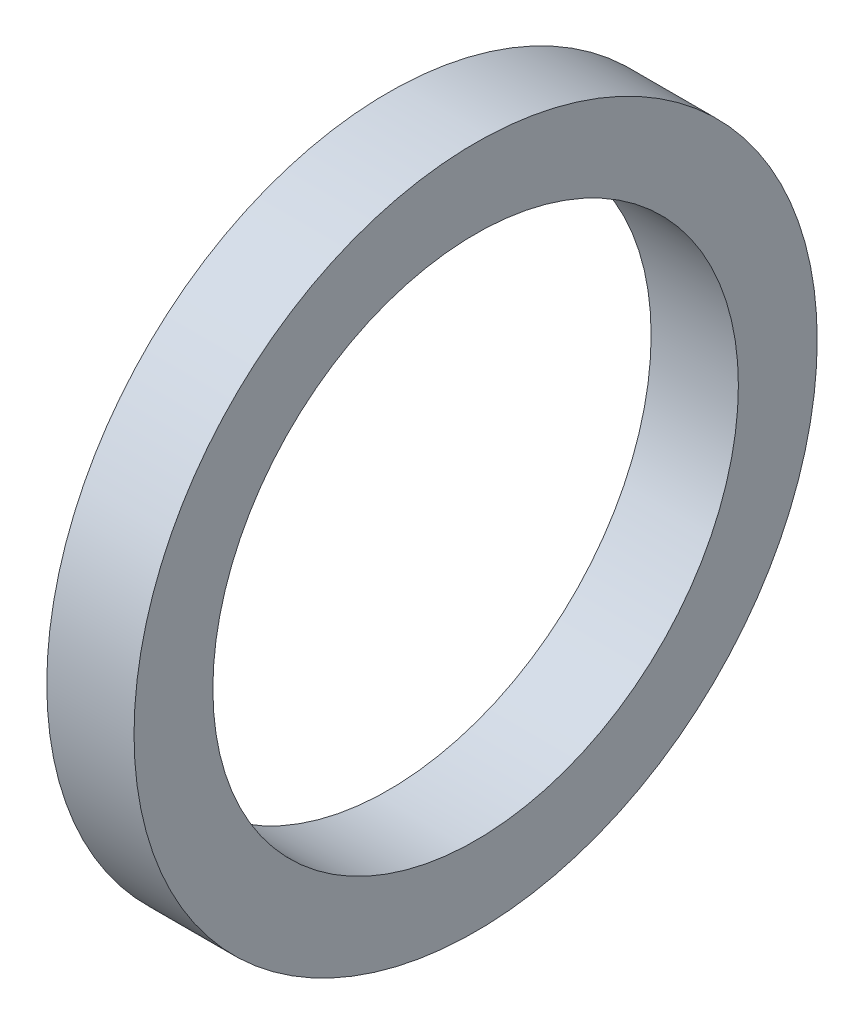
SolidWorks part; units mm, degrees
ref_plane "Front Plane" through (0, 0, 0) normal (0, 0, 1) x (1, 0, 0)
ref_plane "Top Plane" through (0, 0, 0) normal (0, 1, 0) x (1, 0, 0)
ref_plane "Right Plane" through (0, 0, 0) normal (1, 0, 0) x (0, 0, -1)
sketch "Sketch2" plane through (0, 0, 0) normal (0, 0, 1) x (1, 0, 0)
  line L0 (0, 0) -> (58.591, 0) construction
  line L2 (0, 0) -> (18.4, 0)
  line L3 (0, 0) -> (0, 2.5)
  line L4 (0, 2.5) -> (18.4, 2.5)
  line L5 (18.4, 0) -> (18.4, 2.5)
  line L6 (6, 2.5) -> (6, 6)
  line L11 (6, 6) -> (9.97, 6)
  line L16 (12.97, 6) -> (12.97, 3)
  line L17 (12.97, 3) -> (13.6304, 3)
  line L18 (13.6304, 3) -> (13.6304, 2.5)
  line L19 (13.6304, 2.5) -> (6, 2.5)
  line L22 (13.6304, 2.5) -> (16.1104, 2.5)
  line L23 (13.6304, 2.5) -> (13.6304, 4)
  line L24 (13.6304, 4) -> (16.1104, 4)
  line L25 (16.1104, 2.5) -> (16.1104, 4)
  line L27 (6, 6) -> (9.97, 6)
  line L28 (6, 6) -> (6, 9)
  line L29 (6, 9) -> (9.97, 9)
  line L30 (9.97, 6) -> (9.97, 9)
  line L31 (6, 9) -> (6, 8.25)
  line L32 (6, 8.25) -> (5, 8.25)
  line L33 (8.58, 22.001) -> (8.58, 12.476) construction
  line L34 (5, 12.476) -> (12.16, 12.476)
  line L35 (9.97, 9) -> (12.16, 9)
  line L36 (5, 7.5) -> (3, 7.5)
  line L37 (5, 8.25) -> (5, 12.476)
  line L38 (5, 7.5) -> (5, 14)
  line L39 (5, 14) -> (3, 14)
  line L40 (3, 7.5) -> (3, 14)
  line L41 (5, 22.001) -> (12.16, 22.001)
  line L42 (5, 22.001) -> (5, 30.1625)
  line L43 (5, 30.1625) -> (12.16, 30.1625)
  line L44 (12.16, 22.001) -> (12.16, 30.1625)
  line L49 (16.6304, 22.001) -> (16.6304, 7.5)
  line L51 (23.0104, 7.5) -> (23.0104, 6.5)
  line L54 (16.1104, 4) -> (13.6304, 4)
  line L56 (18.0304, 7.5) -> (23.0104, 7.5)
  line L57 (13.16, 22.001) -> (16.6304, 22.001)
  line L58 (16.1104, 3.5) -> (20.0104, 3.5)
  line L59 (29.9004, 14) -> (26.9004, 11)
  line L60 (4, 31.75) -> (18.0304, 31.75)
  line L61 (18.0304, 7.5) -> (23.0104, 7.5)
  line L62 (18.0304, 7.5) -> (18.0304, 12)
  line L63 (18.0304, 12) -> (23.0104, 12)
  line L64 (23.0104, 7.5) -> (23.0104, 12)
  line L65 (18.0304, 31.75) -> (18.0304, 12)
  line L66 (23.0104, 11) -> (26.9004, 11)
  line L67 (34.8004, 23) -> (31.3004, 19.5)
  line L68 (35.8004, 31) -> (38.7904, 33.99)
  line L69 (29.9004, 14) -> (29.9004, 15)
  line L70 (29.9004, 15) -> (22.9304, 15)
  line L71 (22.9304, 15) -> (21.0304, 15)
  line L72 (18.0304, 7.5) -> (16.6304, 7.5)
  line L73 (21.0304, 15) -> (21.0304, 43)
  line L74 (20.0304, 40) -> (10.0704, 40)
  line L75 (10.0704, 40) -> (4, 40)
  line L76 (21.0304, 43) -> (20.0304, 43)
  line L77 (22.9304, 15) -> (29.9004, 15)
  line L78 (22.9304, 15) -> (22.9304, 21)
  line L79 (22.9304, 21) -> (29.9004, 21)
  line L80 (29.9004, 15) -> (29.9004, 21)
  line L81 (10.0704, 40) -> (20.0304, 40)
  line L82 (10.0704, 40) -> (10.0704, 50)
  line L83 (10.0704, 50) -> (20.0304, 50)
  line L84 (20.0304, 40) -> (20.0304, 50)
  line L85 (4, 40) -> (4, 31.75)
  line L86 (12.97, 3) -> (12.97, 2.5)
  line L87 (31.3004, 19.5) -> (29.9004, 19.5)
  line L88 (21.51, 63.5) -> (21.51, 44)
  line L89 (21.51, 63.5) -> (25.9304, 63.5)
  line L90 (25.9304, 63.5) -> (25.9304, 25)
  line L91 (27.8304, 25) -> (25.9304, 25)
  line L92 (10.0704, 48) -> (9, 48)
  line L93 (9, 48) -> (9, 53.476)
  line L94 (9, 53.476) -> (20.0304, 53.476)
  line L95 (20.0304, 53.476) -> (20.0304, 50)
  line L96 (14.5152, 63.001) -> (14.5152, 53.476) construction
  line L97 (9, 63.001) -> (20.0304, 63.001)
  line L98 (9, 63.001) -> (9, 68.2625)
  line L99 (9, 68.2625) -> (20.0304, 68.2625)
  line L100 (20.0304, 63.001) -> (20.0304, 68.2625)
  line L101 (12.97, 6) -> (11.97, 6)
  line L102 (9, 42.5) -> (5, 42.5)
  line L103 (9, 42.5) -> (9, 55)
  line L104 (9, 55) -> (5, 55)
  line L105 (5, 42.5) -> (5, 55)
  line L106 (9.97, 6) -> (10.87, 6)
  line L107 (27.8304, 25) -> (34.8004, 25)
  line L108 (34.8004, 25) -> (34.8004, 23)
  line L109 (0, 0) -> (-2, 0)
  line L110 (0, 0) -> (0, 11)
  line L111 (27.8304, 25) -> (34.8004, 25)
  line L112 (27.8304, 25) -> (27.8304, 32.5)
  line L113 (27.8304, 32.5) -> (34.8004, 32.5)
  line L114 (34.8004, 25) -> (34.8004, 32.5)
  line L115 (35.8004, 31) -> (34.8004, 31)
  line L116 (27.8304, 32.5) -> (27.8304, 64.5)
  line L117 (21.1827, 74.025) -> (6.8477, 74.025)
  line L118 (6.8477, 74.025) -> (6.8477, 76.2)
  line L119 (38.7904, 47.29) -> (30.8304, 55.25)
  line L120 (0, 11) -> (-2, 11)
  line L121 (38.7904, 43.815) -> (30.8529, 43.815)
  line L123 (-4.8, 69.85) -> (1.55, 76.2)
  line L124 (38.7904, 47.29) -> (38.7904, 33.99)
  line L125 (-2, 0) -> (-2, 11)
  line L126 (38.7904, 37.465) -> (30.8529, 37.465)
  line L127 (30.8529, 43.815) -> (30.8529, 37.465)
  line L128 (6, 2.5) -> (6, 0)
  line L129 (0, 63.5) -> (0, 30)
  line L132 (5, 63.5) -> (0, 63.5)
  line L136 (-1.8, 30) -> (-11.76, 30)
  line L138 (-13.76, 25.4) -> (-2, 25.4)
  line L139 (-2, 25.4) -> (-2, 11.5)
  line L140 (27.8304, 64.5) -> (21.1827, 64.5)
  line L141 (-1.8, 30) -> (-11.76, 30)
  line L142 (-1.8, 30) -> (-1.8, 39)
  line L143 (-1.8, 39) -> (-11.76, 39)
  line L144 (-11.76, 30) -> (-11.76, 39)
  line L145 (21.1827, 64.5) -> (21.1827, 74.025)
  line L146 (-12.76, 37) -> (-12.76, 47.29)
  line L147 (-12.76, 37) -> (-11.76, 37)
  line L148 (30.8304, 55.25) -> (30.8304, 76.2)
  line L149 (11.97, 6) -> (11.97, 5.45)
  line L154 (-2, 11.5) -> (1, 11.5)
  line L155 (5, 60.6197) -> (24.05, 60.6197)
  line L160 (5, 60.6197) -> (5, 55.8572)
  line L161 (5, 55.8572) -> (24.05, 55.8572)
  line L166 (24.05, 60.6197) -> (24.05, 55.8572)
  line L167 (5, 60.6197) -> (24.05, 55.8572) construction
  line L172 (5, 55.8572) -> (24.05, 60.6197) construction
  line L173 (24.05, 62.2072) -> (25.9304, 62.2072)
  line L174 (11.97, 5.45) -> (10.87, 5.45)
  line L175 (10.87, 6) -> (10.87, 5.45)
  line L176 (24.05, 62.2072) -> (24.05, 54.2697)
  line L177 (24.05, 54.2697) -> (25.9304, 54.2697)
  line L178 (25.9304, 62.2072) -> (25.9304, 54.2697)
  line L179 (24.05, 62.2072) -> (25.9304, 54.2697) construction
  line L180 (24.05, 54.2697) -> (25.9304, 62.2072) construction
  line L181 (3, 19.6197) -> (15.7, 19.6197)
  line L182 (3, 19.6197) -> (3, 14.8572)
  line L183 (3, 14.8572) -> (15.7, 14.8572)
  line L184 (15.7, 19.6197) -> (15.7, 14.8572)
  line L185 (3, 19.6197) -> (15.7, 14.8572) construction
  line L186 (3, 14.8572) -> (15.7, 19.6197) construction
  line L187 (15.7, 21.2072) -> (16.6304, 21.2072)
  line L188 (15.7, 21.2072) -> (15.7, 13.2697)
  line L189 (15.7, 13.2697) -> (16.6304, 13.2697)
  line L190 (16.6304, 21.2072) -> (16.6304, 13.2697)
  line L191 (15.7, 21.2072) -> (16.6304, 13.2697) construction
  line L192 (15.7, 13.2697) -> (16.6304, 21.2072) construction
  line L193 (1, 11.5) -> (1, 6.5)
  line L194 (1, 6.5) -> (3, 6.5)
  line L195 (23.0104, 6.5) -> (20.0104, 3.5)
  line L196 (5, 63.5) -> (5, 42.5)
  line L197 (5, 42.5) -> (3, 42.5)
  line L198 (3, 42.5) -> (3, 6.5)
  line L199 (6, 0) -> (12.97, 0)
  line L200 (12.97, 0) -> (12.97, 2.5)
  line L201 (18.0304, 31.75) -> (18.0304, 35.875)
  line L202 (18.0304, 35.875) -> (21.0304, 35.875)
  line L203 (30.8304, 76.2) -> (6.8477, 76.2)
  line L204 (3.4027, 69.85) -> (7.8477, 69.85) construction
  line L205 (7.8477, 67.4687) -> (26.8977, 67.4688)
  line L206 (7.8477, 74.025) -> (7.8477, 64.5)
  line L207 (7.8477, 64.5) -> (-1.8, 64.5)
  line L208 (-1.8, 64.5) -> (-1.8, 39)
  line L209 (-12.76, 47.29) -> (-4.8, 55.25)
  line L210 (-4.8, 55.25) -> (-4.8, 69.85)
  line L211 (7.8477, 67.4687) -> (7.8477, 72.2313)
  line L212 (7.8477, 72.2313) -> (26.8977, 72.2313)
  line L213 (26.8977, 67.4688) -> (26.8977, 72.2313)
  line L214 (26.8977, 73.8187) -> (30.8304, 73.8187)
  line L215 (26.8977, 73.8187) -> (26.8977, 65.8813)
  line L216 (26.8977, 65.8813) -> (30.8304, 65.8813)
  line L217 (30.8304, 73.8187) -> (30.8304, 65.8813)
  line L218 (3.4027, 72.2313) -> (25.6277, 72.2313)
  line L219 (3.4027, 72.2313) -> (3.4027, 67.4687)
  line L220 (3.4027, 67.4687) -> (25.6277, 67.4687)
  line L221 (25.6277, 72.2313) -> (25.6277, 67.4687)
  line L222 (25.6277, 69.85) -> (21.1827, 69.85) construction
  line L223 (21.51, 44) -> (22.9304, 44)
  line L224 (22.9304, 44) -> (22.9304, 21)
  line L225 (13.6304, 4) -> (13.6304, 12.2697)
  line L226 (13.6304, 12.2697) -> (13.16, 12.2697)
  line L227 (13.16, 12.2697) -> (13.16, 22.001)
  line L228 (12.16, 9) -> (12.16, 12.476)
  line L229 (-1.8, 30) -> (0, 30)
  line L230 (9, 65.6317) -> (3.4027, 65.6317) construction
  line L231 (20.0304, 65.6317) -> (25.6277, 65.6317) construction
  line L232 (1.55, 76.2) -> (6.8477, 76.2)
  line L233 (-11.76, 30) -> (-13.76, 30)
  line L234 (-13.76, 30) -> (-13.76, 25.4)
  circle A0 centre (26.8804, 25.95) radius 0.95
  circle A1 centre (21.9804, 15.95) radius 0.95
  circle A2 centre (17.3304, 8.2) radius 0.7
  circle A3 centre (10.42, 6.45) radius 0.45
  circle A4 centre (-0.9, 30.9) radius 0.9
  point P7 (24.9902, 58.2385)
  point P131 (16.1652, 17.2385)
  point P135 (14.525, 58.2385)
  point P146 (9.35, 17.2385)
sketch "Sketch3" plane through (0, 0, 0) normal (0, 0, 1) x (1, 0, 0)
  line L0 (-1.8, 30) -> (-1.8, 39) construction
  line L1 (-1.8, 30) -> (-11.76, 30) construction
  line L2 (-11.76, 30) -> (-11.76, 39) construction
  line L3 (-1.8, 39) -> (-11.76, 39) construction
  line L4 (-1.8, 30) -> (-1.8, 39)
  line L5 (-1.8, 30) -> (-11.76, 30)
  line L6 (-11.76, 30) -> (-11.76, 39)
  line L7 (-1.8, 39) -> (-11.76, 39)
revolve "Revolve1" add sketch "Sketch3" angle 360 about L0
